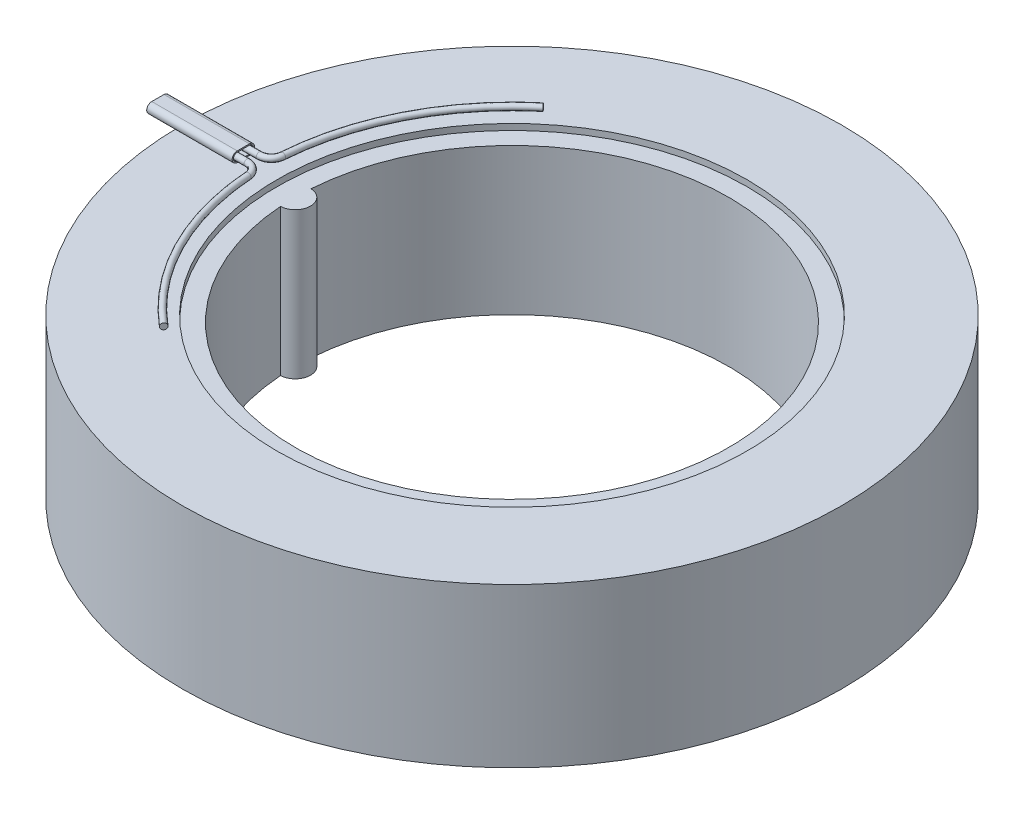
SolidWorks part; units mm, degrees
ref_plane "Front Plane" through (0, 0, 0) normal (0, 0, 1) x (1, 0, 0)
ref_plane "Top Plane" through (0, 0, 0) normal (0, 1, 0) x (1, 0, 0)
ref_plane "Right Plane" through (0, 0, 0) normal (1, 0, 0) x (0, 0, -1)
ref_axis "Axis1" through (0, 0, 0) along (0, 1, 0)
sketch "Sketch1" plane through (0, 0, 0) normal (0, 0, 1) x (1, 0, 0)
  line L0 (0, 0) -> (0, -11959.2771) construction
  line L1 (-17.75, 6) -> (-17.75, -6)
  line L2 (-17.75, 6) -> (-19.25, 6)
  line L3 (-19.25, 6) -> (-19.25, -6)
  line L4 (-19.25, -6) -> (-17.75, -6)
  point P5 (-17.75, 0)
  dimension "D1" = 35.5
  dimension "D2" = 12
  dimension "D3" = 1.5
revolve "Revolve1" add sketch "Sketch1" angle 360 about L0
sketch "Sketch2" plane through (0, 0, 0) normal (0, 0, 1) x (1, 0, 0)
  line L0 (-19.25, 6) -> (-19.25, -6) construction
  line L1 (-19.25, 6.5) -> (-27, 6.5)
  line L2 (-19.25, 6.5) -> (-19.25, -6.5)
  line L3 (-19.25, -6.5) -> (-27, -6.5)
  line L4 (-27, 6.5) -> (-27, -6.5)
  point P6 (-19.25, 0)
  dimension "D1" = 13
  dimension "D2" = 27
revolve "Revolve2" add sketch "Sketch2" angle 360 about L0
sketch "Sketch3" plane through (0, 0, 0) normal (0, 1, 0) x (1, 0, 0)
  circle A0 centre (-17.75, 0) radius 1.25
  circle A1 centre (0, 0) radius 17.75 construction
  dimension "D1" = 2.5
extrude "Boss-Extrude1" add sketch "Sketch3" along normal up to surface and the other way up to surface up to face at (0, 6, 19.25) other way up to face at (0, -6, 17.75)
ref_plane "Plane1" through (0, 7, 0) normal (0, 1, 0) x (1, 0, 0)
sketch "Sketch4" plane through (0, 7, 0) normal (0, 1, 0) x (1, 0, 0)
  line L0 (0, 0) -> (-50000, 0) construction
  line L1 (-25.8074, 0.5) -> (-21.197, 0.5)
  arc A0 (-20.1995, 1.4294) -> (-12.9841, 15.5395) centre (0, 0) cw
  arc A1 (-21.197, 0.5) -> (-20.1995, 1.4294) centre (-21.197, 1.5) ccw
  circle A2 centre (0, 0) radius 19.25 construction
  dimension "D1" = 1
  dimension "D2" = 1
  dimension "D3" = 1
sweep "Sweep1" add path "Sketch4" circular profile diameter 0.5 parameters "D3"=0.5
mirror "Mirror2" about plane through (0, 0, 0) normal (0, 0, 1) of bodies 104
sketch "Sketch23" plane through (0, 0, 0) normal (1, 0, 0) x (0, 0, -1)
  line L0 (0.5, 7) -> (-0.5, 7) construction
  line L1 (0.5, 6.6851) -> (-0.5, 6.6851)
  line L2 (0.5, 7.3149) -> (-0.5, 7.3149)
  arc A0 (0.5, 6.6851) -> (0.5, 7.3149) centre (0.5, 7) ccw
  arc A1 (-0.5, 7.3149) -> (-0.5, 6.6851) centre (-0.5, 7) ccw
  point P4 (0, 7)
extrude "Extrude-Thin1" add sketch "Sketch23" against normal blind 7 from offset 22 separate body thin offset against normal yes thin type one direction wall 0.1
